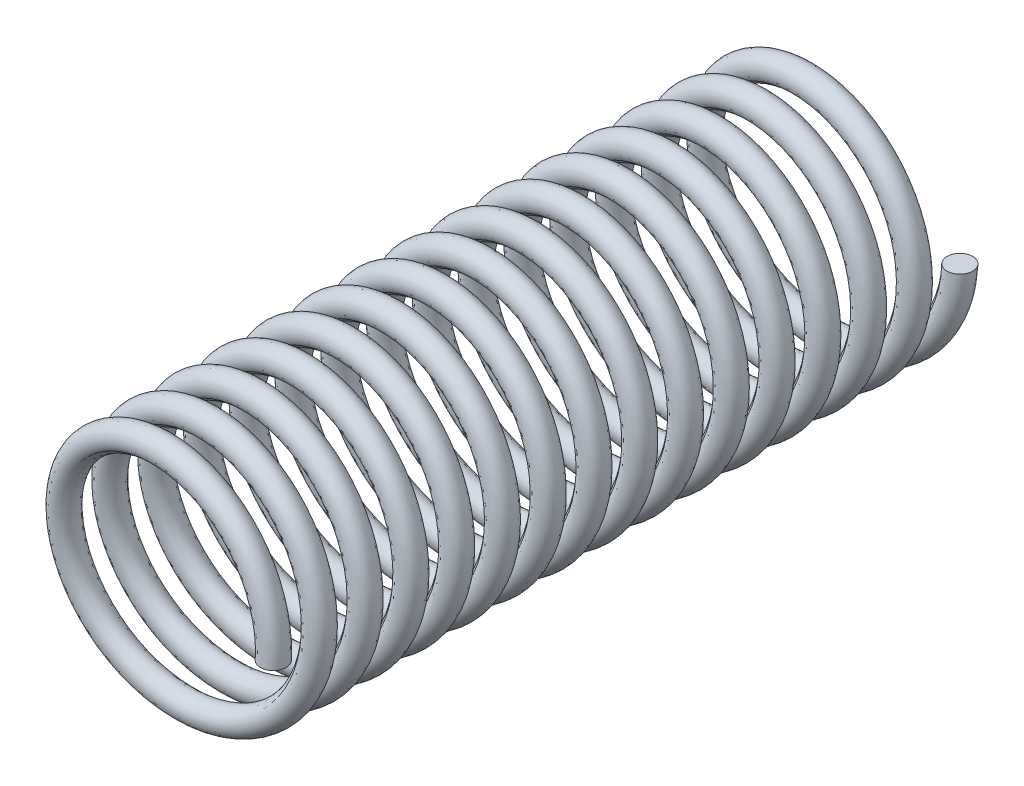
SolidWorks part; units mm, degrees
ref_plane "Front Plane" through (0, 0, 0) normal (0, 0, 1) x (1, 0, 0)
ref_plane "Top Plane" through (0, 0, 0) normal (0, 1, 0) x (1, 0, 0)
ref_plane "Right Plane" through (0, 0, 0) normal (1, 0, 0) x (0, 0, -1)
sketch "Sketch1" plane through (0, 0, 0) normal (0, 0, 1) x (1, 0, 0)
  circle A0 centre (0, 0) radius 3.2163
  dimension "D1" = 6.4325
curve "Helix/Spiral1" pitch 1.27 height 19.05 radius 3.2163 left hand yes centre (0, 0, 0) axis (0, 0, 1) start towards (1, 0, 0)
sketch "Sketch2" plane through (0, 0, 0) normal (0, 1, 0) x (1, 0, 0)
  circle A0 centre (3.2163, 0) radius 0.3556
  spline S0 degree 3 poles (3.2163, 0) (3.2163, -0.0263) (3.0488, -0.0795) (2.3335, -0.1587) (1.2629, -0.2381) (0, -0.3175) (-1.2629, -0.3969) (-2.3335, -0.4762) (-3.0488, -0.5556) (-3.3, -0.635) (-3.0488, -0.7144) (-2.3335, -0.7937) (-1.2629, -0.8731) (0, -0.9525) (1.2629, -1.0319) (2.3335, -1.1112) (3.0488, -1.1906) (3.3, -1.27) (3.0488, -1.3494) (2.3335, -1.4287) (1.2629, -1.5081) (0, -1.5875) (-1.2629, -1.6669) (-2.3335, -1.7463) (-3.0488, -1.8256) (-3.3, -1.905) (-3.0488, -1.9844) (-2.3335, -2.0637) (-1.2629, -2.1431) (0, -2.2225) (1.2629, -2.3019) (2.3335, -2.3813) (3.0488, -2.4606) (3.3, -2.54) (3.0488, -2.6194) (2.3335, -2.6988) (1.2629, -2.7781) (0, -2.8575) (-1.2629, -2.9369) (-2.3335, -3.0162) (-3.0488, -3.0956) (-3.3, -3.175) (-3.0488, -3.2544) (-2.3335, -3.3338) (-1.2629, -3.4131) (0, -3.4925) (1.2629, -3.5719) (2.3335, -3.6512) (3.0488, -3.7306) (3.3, -3.81) (3.0488, -3.8894) (2.3335, -3.9687) (1.2629, -4.0481) (0, -4.1275) (-1.2629, -4.2069) (-2.3335, -4.2862) (-3.0488, -4.3656) (-3.3, -4.445) (-3.0488, -4.5244) (-2.3335, -4.6037) (-1.2629, -4.6831) (0, -4.7625) (1.2629, -4.8419) (2.3335, -4.9212) (3.0488, -5.0006) (3.3, -5.08) (3.0488, -5.1594) (2.3335, -5.2387) (1.2629, -5.3181) (0, -5.3975) (-1.2629, -5.4769) (-2.3335, -5.5562) (-3.0488, -5.6356) (-3.3, -5.715) (-3.0488, -5.7944) (-2.3335, -5.8737) (-1.2629, -5.9531) (0, -6.0325) (1.2629, -6.1119) (2.3335, -6.1912) (3.0488, -6.2706) (3.3, -6.35) (3.0488, -6.4294) (2.3335, -6.5087) (1.2629, -6.5881) (0, -6.6675) (-1.2629, -6.7469) (-2.3335, -6.8262) (-3.0488, -6.9056) (-3.3, -6.985) (-3.0488, -7.0644) (-2.3335, -7.1437) (-1.2629, -7.2231) (0, -7.3025) (1.2629, -7.3819) (2.3335, -7.4612) (3.0488, -7.5406) (3.3, -7.62) (3.0488, -7.6994) (2.3335, -7.7787) (1.2629, -7.8581) (0, -7.9375) (-1.2629, -8.0169) (-2.3335, -8.0962) (-3.0488, -8.1756) (-3.3, -8.255) (-3.0488, -8.3344) (-2.3335, -8.4137) (-1.2629, -8.4931) (0, -8.5725) (1.2629, -8.6519) (2.3335, -8.7312) (3.0488, -8.8106) (3.3, -8.89) (3.0488, -8.9694) (2.3335, -9.0487) (1.2629, -9.1281) (0, -9.2075) (-1.2629, -9.2869) (-2.3335, -9.3662) (-3.0488, -9.4456) (-3.3, -9.525) (-3.0488, -9.6044) (-2.3335, -9.6837) (-1.2629, -9.7631) (0, -9.8425) (1.2629, -9.9219) (2.3335, -10.0012) (3.0488, -10.0806) (3.3, -10.16) (3.0488, -10.2394) (2.3335, -10.3187) (1.2629, -10.3981) (0, -10.4775) (-1.2629, -10.5569) (-2.3335, -10.6362) (-3.0488, -10.7156) (-3.3, -10.795) (-3.0488, -10.8744) (-2.3335, -10.9537) (-1.2629, -11.0331) (0, -11.1125) (1.2629, -11.1919) (2.3335, -11.2712) (3.0488, -11.3506) (3.3, -11.43) (3.0488, -11.5094) (2.3335, -11.5887) (1.2629, -11.6681) (0, -11.7475) (-1.2629, -11.8269) (-2.3335, -11.9062) (-3.0488, -11.9856) (-3.3, -12.065) (-3.0488, -12.1444) (-2.3335, -12.2237) (-1.2629, -12.3031) (0, -12.3825) (1.2629, -12.4619) (2.3335, -12.5412) (3.0488, -12.6206) (3.3, -12.7) (3.0488, -12.7794) (2.3335, -12.8587) (1.2629, -12.9381) (0, -13.0175) (-1.2629, -13.0969) (-2.3335, -13.1762) (-3.0488, -13.2556) (-3.3, -13.335) (-3.0488, -13.4144) (-2.3335, -13.4937) (-1.2629, -13.5731) (0, -13.6525) (1.2629, -13.7319) (2.3335, -13.8112) (3.0488, -13.8906) (3.3, -13.97) (3.0488, -14.0494) (2.3335, -14.1287) (1.2629, -14.2081) (0, -14.2875) (-1.2629, -14.3669) (-2.3335, -14.4462) (-3.0488, -14.5256) (-3.3, -14.605) (-3.0488, -14.6844) (-2.3335, -14.7637) (-1.2629, -14.8431) (0, -14.9225) (1.2629, -15.0019) (2.3335, -15.0812) (3.0488, -15.1606) (3.3, -15.24) (3.0488, -15.3194) (2.3335, -15.3987) (1.2629, -15.4781) (0, -15.5575) (-1.2629, -15.6369) (-2.3335, -15.7162) (-3.0488, -15.7956) (-3.3, -15.875) (-3.0488, -15.9544) (-2.3335, -16.0337) (-1.2629, -16.1131) (0, -16.1925) (1.2629, -16.2719) (2.3335, -16.3512) (3.0488, -16.4306) (3.3, -16.51) (3.0488, -16.5894) (2.3335, -16.6687) (1.2629, -16.7481) (0, -16.8275) (-1.2629, -16.9069) (-2.3335, -16.9862) (-3.0488, -17.0656) (-3.3, -17.145) (-3.0488, -17.2244) (-2.3335, -17.3037) (-1.2629, -17.3831) (0, -17.4625) (1.2629, -17.5419) (2.3335, -17.6212) (3.0488, -17.7006) (3.3, -17.78) (3.0488, -17.8594) (2.3335, -17.9388) (1.2629, -18.0181) (0, -18.0975) (-1.2629, -18.1769) (-2.3335, -18.2563) (-3.0488, -18.3356) (-3.3, -18.415) (-3.0488, -18.4944) (-2.3335, -18.5738) (-1.2629, -18.6531) (0, -18.7325) (1.2629, -18.8119) (2.3335, -18.8913) (3.0488, -18.9705) (3.2163, -19.0237) (3.2163, -19.05) knots 0 0 0 0 0.004167 0.008333 0.0125 0.016667 0.020833 0.025 0.029167 0.033333 0.0375 0.041667 0.045833 0.05 0.054167 0.058333 0.0625 0.066667 0.070833 0.075 0.079167 0.083333 0.0875 0.091667 0.095833 0.1 0.104167 0.108333 0.1125 0.116667 0.120833 0.125 0.129167 0.133333 0.1375 0.141667 0.145833 0.15 0.154167 0.158333 0.1625 0.166667 0.170833 0.175 0.179167 0.183333 0.1875 0.191667 0.195833 0.2 0.204167 0.208333 0.2125 0.216667 0.220833 0.225 0.229167 0.233333 0.2375 0.241667 0.245833 0.25 0.254167 0.258333 0.2625 0.266667 0.270833 0.275 0.279167 0.283333 0.2875 0.291667 0.295833 0.3 0.304167 0.308333 0.3125 0.316667 0.320833 0.325 0.329167 0.333333 0.3375 0.341667 0.345833 0.35 0.354167 0.358333 0.3625 0.366667 0.370833 0.375 0.379167 0.383333 0.3875 0.391667 0.395833 0.4 0.404167 0.408333 0.4125 0.416667 0.420833 0.425 0.429167 0.433333 0.4375 0.441667 0.445833 0.45 0.454167 0.458333 0.4625 0.466667 0.470833 0.475 0.479167 0.483333 0.4875 0.491667 0.495833 0.5 0.504167 0.508333 0.5125 0.516667 0.520833 0.525 0.529167 0.533333 0.5375 0.541667 0.545833 0.55 0.554167 0.558333 0.5625 0.566667 0.570833 0.575 0.579167 0.583333 0.5875 0.591667 0.595833 0.6 0.604167 0.608333 0.6125 0.616667 0.620833 0.625 0.629167 0.633333 0.6375 0.641667 0.645833 0.65 0.654167 0.658333 0.6625 0.666667 0.670833 0.675 0.679167 0.683333 0.6875 0.691667 0.695833 0.7 0.704167 0.708333 0.7125 0.716667 0.720833 0.725 0.729167 0.733333 0.7375 0.741667 0.745833 0.75 0.754167 0.758333 0.7625 0.766667 0.770833 0.775 0.779167 0.783333 0.7875 0.791667 0.795833 0.8 0.804167 0.808333 0.8125 0.816667 0.820833 0.825 0.829167 0.833333 0.8375 0.841667 0.845833 0.85 0.854167 0.858333 0.8625 0.866667 0.870833 0.875 0.879167 0.883333 0.8875 0.891667 0.895833 0.9 0.904167 0.908333 0.9125 0.916667 0.920833 0.925 0.929167 0.933333 0.9375 0.941667 0.945833 0.95 0.954167 0.958333 0.9625 0.966667 0.970833 0.975 0.979167 0.983333 0.9875 0.991667 0.995833 1 1 1 1 construction
  dimension "D1" = 0.7112
sweep "Sweep1" add profiles "Sketch2" path "Helix/Spiral1"
ref_axis "Axis1" through (0, 0, -1.3437) along (0, 0, 1)
sketch "Sketch3" plane through (0, 0, 0) normal (0, 1, 0) x (1, 0, 0)
  circle A0 centre (3.2163, 0) radius 0.3556 construction
  point P0 (3.2163, 0.3556)
sketch "Sketch4" plane through (0, 0, 0) normal (0, -1, 0) x (1, 0, 0)
  circle A0 centre (3.2163, 19.05) radius 0.3556 construction
  point P0 (3.2163, 19.4056)
